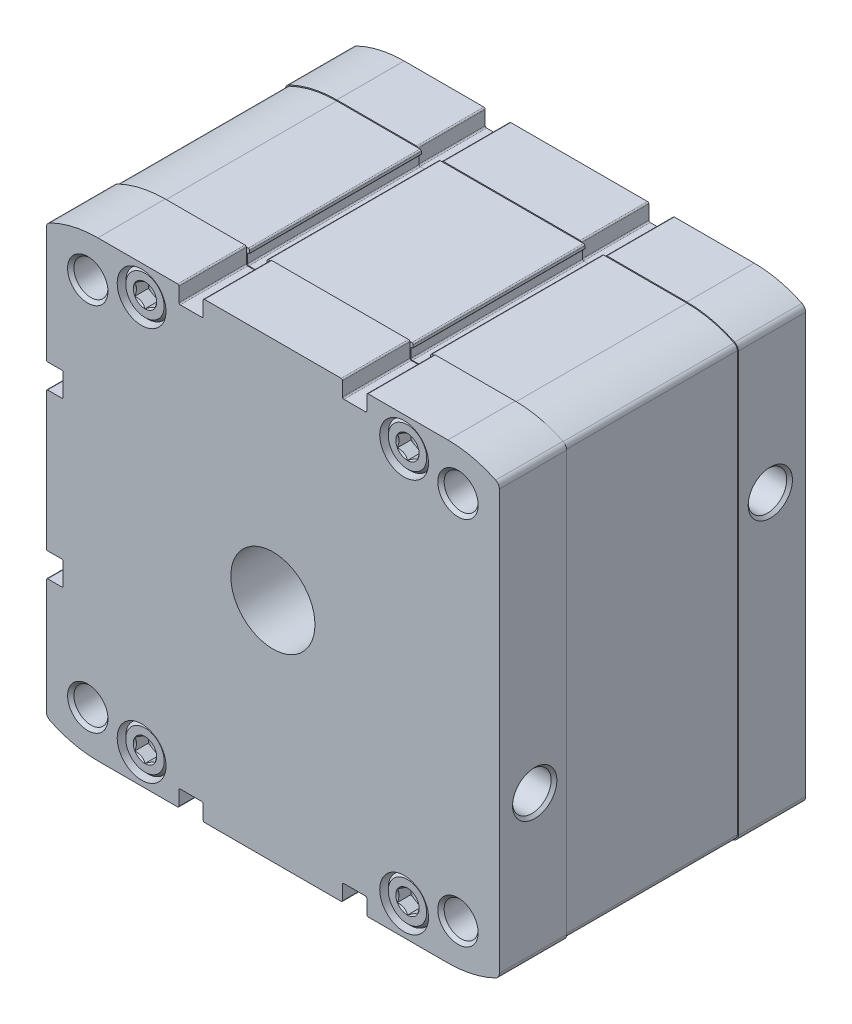
SolidWorks part; units mm, degrees
ref_plane "Front Plane" through (0, 0, 0) normal (0, 0, 1) x (1, 0, 0)
ref_plane "Top Plane" through (0, 0, 0) normal (0, 1, 0) x (1, 0, 0)
ref_plane "Right Plane" through (0, 0, 0) normal (1, 0, 0) x (0, 0, -1)
ref_plane "Plane1" through (0, 0, -20) normal (0, 0, 1) x (1, 0, 0)
ref_plane "Plane2" through (0, 0, -71) normal (0, 0, 1) x (1, 0, 0)
sketch "Sketch1" plane through (0, 0, 0) normal (0, 0, 1) x (1, 0, 0)
  line L0 (-66.9, 27.9) -> (-62.7, 27.9)
  line L1 (-62.3, 27.5) -> (-62.3, 21.1)
  line L2 (-62.7, 20.7) -> (-66.9, 20.7)
  line L3 (-67.3, 20.3) -> (-67.3, -20.3)
  line L4 (-66.9, -20.7) -> (-62.7, -20.7)
  line L5 (-62.3, -21.1) -> (-62.3, -27.5)
  line L6 (-62.7, -27.9) -> (-66.9, -27.9)
  line L7 (-67.3, -28.3) -> (-67.3, -62.3009)
  line L8 (-52, -67.3) -> (-28.3, -67.3)
  line L9 (-27.9, -66.9) -> (-27.9, -62.7)
  line L10 (-27.5, -62.3) -> (-21.1, -62.3)
  line L11 (-20.7, -62.7) -> (-20.7, -66.9)
  line L12 (-20.3, -67.3) -> (20.3, -67.3)
  line L13 (20.7, -66.9) -> (20.7, -62.7)
  line L14 (21.1, -62.3) -> (27.5, -62.3)
  line L15 (27.9, -62.7) -> (27.9, -66.9)
  line L16 (28.3, -67.3) -> (52, -67.3)
  line L17 (67.3, -62.3009) -> (67.3, 62.3009)
  line L18 (52, 67.3) -> (28.3, 67.3)
  line L19 (27.9, 66.9) -> (27.9, 62.7)
  line L20 (27.5, 62.3) -> (21.1, 62.3)
  line L21 (20.7, 62.7) -> (20.7, 66.9)
  line L22 (20.3, 67.3) -> (-20.3, 67.3)
  line L23 (-20.7, 66.9) -> (-20.7, 62.7)
  line L24 (-21.1, 62.3) -> (-27.5, 62.3)
  line L25 (-27.9, 62.7) -> (-27.9, 66.9)
  line L26 (-28.3, 67.3) -> (-52, 67.3)
  line L27 (-67.3, 62.3009) -> (-67.3, 28.3)
  arc A0 (-67.3, 28.3) -> (-66.9, 27.9) centre (-66.9, 28.3) ccw
  arc A1 (-62.7, 27.9) -> (-62.3, 27.5) centre (-62.7, 27.5) cw
  arc A2 (-62.3, 21.1) -> (-62.7, 20.7) centre (-62.7, 21.1) cw
  arc A3 (-66.9, 20.7) -> (-67.3, 20.3) centre (-66.9, 20.3) ccw
  arc A4 (-67.3, -20.3) -> (-66.9, -20.7) centre (-66.9, -20.3) ccw
  arc A5 (-62.7, -20.7) -> (-62.3, -21.1) centre (-62.7, -21.1) cw
  arc A6 (-62.3, -27.5) -> (-62.7, -27.9) centre (-62.7, -27.5) cw
  arc A7 (-66.9, -27.9) -> (-67.3, -28.3) centre (-66.9, -28.3) ccw
  arc A8 (-67.3, -62.3009) -> (-66.1966, -64.0575) centre (-65.35, -62.3009) ccw
  arc A9 (-66.1966, -64.0575) -> (-52, -67.3) centre (-52, -34.6) ccw
  arc A10 (-28.3, -67.3) -> (-27.9, -66.9) centre (-28.3, -66.9) ccw
  arc A11 (-27.9, -62.7) -> (-27.5, -62.3) centre (-27.5, -62.7) cw
  arc A12 (-21.1, -62.3) -> (-20.7, -62.7) centre (-21.1, -62.7) cw
  arc A13 (-20.7, -66.9) -> (-20.3, -67.3) centre (-20.3, -66.9) ccw
  arc A14 (20.3, -67.3) -> (20.7, -66.9) centre (20.3, -66.9) ccw
  arc A15 (20.7, -62.7) -> (21.1, -62.3) centre (21.1, -62.7) cw
  arc A16 (27.5, -62.3) -> (27.9, -62.7) centre (27.5, -62.7) cw
  arc A17 (27.9, -66.9) -> (28.3, -67.3) centre (28.3, -66.9) ccw
  arc A18 (52, -67.3) -> (66.1966, -64.0575) centre (52, -34.6) ccw
  arc A19 (66.1966, -64.0575) -> (67.3, -62.3009) centre (65.35, -62.3009) ccw
  arc A20 (67.3, 62.3009) -> (66.1966, 64.0575) centre (65.35, 62.3009) ccw
  arc A21 (66.1966, 64.0575) -> (52, 67.3) centre (52, 34.6) ccw
  arc A22 (28.3, 67.3) -> (27.9, 66.9) centre (28.3, 66.9) ccw
  arc A23 (27.9, 62.7) -> (27.5, 62.3) centre (27.5, 62.7) cw
  arc A24 (21.1, 62.3) -> (20.7, 62.7) centre (21.1, 62.7) cw
  arc A25 (20.7, 66.9) -> (20.3, 67.3) centre (20.3, 66.9) ccw
  arc A26 (-20.3, 67.3) -> (-20.7, 66.9) centre (-20.3, 66.9) ccw
  arc A27 (-20.7, 62.7) -> (-21.1, 62.3) centre (-21.1, 62.7) cw
  arc A28 (-27.5, 62.3) -> (-27.9, 62.7) centre (-27.5, 62.7) cw
  arc A29 (-27.9, 66.9) -> (-28.3, 67.3) centre (-28.3, 66.9) ccw
  arc A30 (-52, 67.3) -> (-66.1966, 64.0575) centre (-52, 34.6) ccw
  arc A31 (-66.1966, 64.0575) -> (-67.3, 62.3009) centre (-65.35, 62.3009) ccw
extrude "Boss-Extrude1" add sketch "Sketch1" against normal blind 91
sketch "Sketch2" plane through (0, 0, -20) normal (0, 0, 1) x (1, 0, 0)
  line L0 (-67, 67) -> (-67, -67)
  line L1 (-67, -67) -> (67, -67)
  line L2 (67, -67) -> (67, 67)
  line L3 (67, 67) -> (-67, 67)
extrude "Boss-Extrude2" add sketch "Sketch2" against normal blind 51
sketch "Sketch3" plane through (0, 0, -20) normal (0, 0, 1) x (1, 0, 0)
  line L0 (-100, 100) -> (-100, -100)
  line L1 (-100, -100) -> (100, -100)
  line L2 (100, -100) -> (100, 100)
  line L3 (100, 100) -> (-100, 100)
  line L4 (-66.6, 26.9) -> (-65.9, 26.9)
  line L5 (-65.7, 27.1) -> (-65.7, 27.35)
  line L6 (-65.5, 27.55) -> (-62.9, 27.55)
  line L7 (-62.5, 27.15) -> (-62.5, 21.45)
  line L8 (-62.9, 21.05) -> (-65.5, 21.05)
  line L9 (-65.7, 21.25) -> (-65.7, 21.5)
  line L10 (-65.9, 21.7) -> (-66.6, 21.7)
  line L11 (-67, 21.3) -> (-67, -21.3)
  line L12 (-66.6, -21.7) -> (-65.9, -21.7)
  line L13 (-65.7, -21.5) -> (-65.7, -21.25)
  line L14 (-65.5, -21.05) -> (-62.9, -21.05)
  line L15 (-62.5, -21.45) -> (-62.5, -27.15)
  line L16 (-62.9, -27.55) -> (-65.5, -27.55)
  line L17 (-65.7, -27.35) -> (-65.7, -27.1)
  line L18 (-65.9, -26.9) -> (-66.6, -26.9)
  line L19 (-67, -27.3) -> (-67, -62.2695)
  line L20 (-52, -67) -> (-27.3, -67)
  line L21 (-26.9, -66.6) -> (-26.9, -65.9)
  line L22 (-27.1, -65.7) -> (-27.35, -65.7)
  line L23 (-27.55, -65.5) -> (-27.55, -62.9)
  line L24 (-27.15, -62.5) -> (-21.45, -62.5)
  line L25 (-21.05, -62.9) -> (-21.05, -65.5)
  line L26 (-21.25, -65.7) -> (-21.5, -65.7)
  line L27 (-21.7, -65.9) -> (-21.7, -66.6)
  line L28 (-21.3, -67) -> (21.3, -67)
  line L29 (21.7, -66.6) -> (21.7, -65.9)
  line L30 (21.5, -65.7) -> (21.25, -65.7)
  line L31 (21.05, -65.5) -> (21.05, -62.9)
  line L32 (21.45, -62.5) -> (27.15, -62.5)
  line L33 (27.55, -62.9) -> (27.55, -65.5)
  line L34 (27.35, -65.7) -> (27.1, -65.7)
  line L35 (26.9, -65.9) -> (26.9, -66.6)
  line L36 (27.3, -67) -> (52, -67)
  line L37 (67, -62.2695) -> (67, 62.2695)
  line L38 (52, 67) -> (27.3, 67)
  line L39 (26.9, 66.6) -> (26.9, 65.9)
  line L40 (27.1, 65.7) -> (27.35, 65.7)
  line L41 (27.55, 65.5) -> (27.55, 62.9)
  line L42 (27.15, 62.5) -> (21.45, 62.5)
  line L43 (21.05, 62.9) -> (21.05, 65.5)
  line L44 (21.25, 65.7) -> (21.5, 65.7)
  line L45 (21.7, 65.9) -> (21.7, 66.6)
  line L46 (21.3, 67) -> (-21.3, 67)
  line L47 (-21.7, 66.6) -> (-21.7, 65.9)
  line L48 (-21.5, 65.7) -> (-21.25, 65.7)
  line L49 (-21.05, 65.5) -> (-21.05, 62.9)
  line L50 (-21.45, 62.5) -> (-27.15, 62.5)
  line L51 (-27.55, 62.9) -> (-27.55, 65.5)
  line L52 (-27.35, 65.7) -> (-27.1, 65.7)
  line L53 (-26.9, 65.9) -> (-26.9, 66.6)
  line L54 (-27.3, 67) -> (-52, 67)
  line L55 (-67, 62.2695) -> (-67, 27.3)
  arc A0 (-67, 27.3) -> (-66.6, 26.9) centre (-66.6, 27.3) ccw
  arc A1 (-65.9, 26.9) -> (-65.7, 27.1) centre (-65.9, 27.1) ccw
  arc A2 (-65.7, 27.35) -> (-65.5, 27.55) centre (-65.5, 27.35) cw
  arc A3 (-62.9, 27.55) -> (-62.5, 27.15) centre (-62.9, 27.15) cw
  arc A4 (-62.5, 21.45) -> (-62.9, 21.05) centre (-62.9, 21.45) cw
  arc A5 (-65.5, 21.05) -> (-65.7, 21.25) centre (-65.5, 21.25) cw
  arc A6 (-65.7, 21.5) -> (-65.9, 21.7) centre (-65.9, 21.5) ccw
  arc A7 (-66.6, 21.7) -> (-67, 21.3) centre (-66.6, 21.3) ccw
  arc A8 (-67, -21.3) -> (-66.6, -21.7) centre (-66.6, -21.3) ccw
  arc A9 (-65.9, -21.7) -> (-65.7, -21.5) centre (-65.9, -21.5) ccw
  arc A10 (-65.7, -21.25) -> (-65.5, -21.05) centre (-65.5, -21.25) cw
  arc A11 (-62.9, -21.05) -> (-62.5, -21.45) centre (-62.9, -21.45) cw
  arc A12 (-62.5, -27.15) -> (-62.9, -27.55) centre (-62.9, -27.15) cw
  arc A13 (-65.5, -27.55) -> (-65.7, -27.35) centre (-65.5, -27.35) cw
  arc A14 (-65.7, -27.1) -> (-65.9, -26.9) centre (-65.9, -27.1) ccw
  arc A15 (-66.6, -26.9) -> (-67, -27.3) centre (-66.6, -27.3) ccw
  arc A16 (-67, -62.2695) -> (-66.0365, -63.8017) centre (-65.3, -62.2695) ccw
  arc A17 (-66.0365, -63.8017) -> (-52, -67) centre (-52, -34.6) ccw
  arc A18 (-27.3, -67) -> (-26.9, -66.6) centre (-27.3, -66.6) ccw
  arc A19 (-26.9, -65.9) -> (-27.1, -65.7) centre (-27.1, -65.9) ccw
  arc A20 (-27.35, -65.7) -> (-27.55, -65.5) centre (-27.35, -65.5) cw
  arc A21 (-27.55, -62.9) -> (-27.15, -62.5) centre (-27.15, -62.9) cw
  arc A22 (-21.45, -62.5) -> (-21.05, -62.9) centre (-21.45, -62.9) cw
  arc A23 (-21.05, -65.5) -> (-21.25, -65.7) centre (-21.25, -65.5) cw
  arc A24 (-21.5, -65.7) -> (-21.7, -65.9) centre (-21.5, -65.9) ccw
  arc A25 (-21.7, -66.6) -> (-21.3, -67) centre (-21.3, -66.6) ccw
  arc A26 (21.3, -67) -> (21.7, -66.6) centre (21.3, -66.6) ccw
  arc A27 (21.7, -65.9) -> (21.5, -65.7) centre (21.5, -65.9) ccw
  arc A28 (21.25, -65.7) -> (21.05, -65.5) centre (21.25, -65.5) cw
  arc A29 (21.05, -62.9) -> (21.45, -62.5) centre (21.45, -62.9) cw
  arc A30 (27.15, -62.5) -> (27.55, -62.9) centre (27.15, -62.9) cw
  arc A31 (27.55, -65.5) -> (27.35, -65.7) centre (27.35, -65.5) cw
  arc A32 (27.1, -65.7) -> (26.9, -65.9) centre (27.1, -65.9) ccw
  arc A33 (26.9, -66.6) -> (27.3, -67) centre (27.3, -66.6) ccw
  arc A34 (52, -67) -> (66.0365, -63.8017) centre (52, -34.6) ccw
  arc A35 (66.0365, -63.8017) -> (67, -62.2695) centre (65.3, -62.2695) ccw
  arc A36 (67, 62.2695) -> (66.0365, 63.8017) centre (65.3, 62.2695) ccw
  arc A37 (66.0365, 63.8017) -> (52, 67) centre (52, 34.6) ccw
  arc A38 (27.3, 67) -> (26.9, 66.6) centre (27.3, 66.6) ccw
  arc A39 (26.9, 65.9) -> (27.1, 65.7) centre (27.1, 65.9) ccw
  arc A40 (27.35, 65.7) -> (27.55, 65.5) centre (27.35, 65.5) cw
  arc A41 (27.55, 62.9) -> (27.15, 62.5) centre (27.15, 62.9) cw
  arc A42 (21.45, 62.5) -> (21.05, 62.9) centre (21.45, 62.9) cw
  arc A43 (21.05, 65.5) -> (21.25, 65.7) centre (21.25, 65.5) cw
  arc A44 (21.5, 65.7) -> (21.7, 65.9) centre (21.5, 65.9) ccw
  arc A45 (21.7, 66.6) -> (21.3, 67) centre (21.3, 66.6) ccw
  arc A46 (-21.3, 67) -> (-21.7, 66.6) centre (-21.3, 66.6) ccw
  arc A47 (-21.7, 65.9) -> (-21.5, 65.7) centre (-21.5, 65.9) ccw
  arc A48 (-21.25, 65.7) -> (-21.05, 65.5) centre (-21.25, 65.5) cw
  arc A49 (-21.05, 62.9) -> (-21.45, 62.5) centre (-21.45, 62.9) cw
  arc A50 (-27.15, 62.5) -> (-27.55, 62.9) centre (-27.15, 62.9) cw
  arc A51 (-27.55, 65.5) -> (-27.35, 65.7) centre (-27.35, 65.5) cw
  arc A52 (-27.1, 65.7) -> (-26.9, 65.9) centre (-27.1, 65.9) ccw
  arc A53 (-26.9, 66.6) -> (-27.3, 67) centre (-27.3, 66.6) ccw
  arc A54 (-52, 67) -> (-66.0365, 63.8017) centre (-52, 34.6) ccw
  arc A55 (-66.0365, 63.8017) -> (-67, 62.2695) centre (-65.3, 62.2695) ccw
extrude "Cut-Extrude1" cut sketch "Sketch3" against normal blind 51
ref_plane "Plane3" through (0, -21.15, 0) normal (0, 1, 0) x (1, 0, 0)
ref_plane "Plane4" through (0, 21.15, 0) normal (0, 1, 0) x (1, 0, 0)
ref_plane "Plane5" through (67.3, 0, 0) normal (1, 0, 0) x (0, 0, -1)
ref_plane "Plane6" through (0, 0, -91) normal (0, 0, 1) x (1, 0, 0)
sketch "Sketch4" plane through (0, -21.15, 0) normal (0, 1, 0) x (1, 0, 0)
  line L0 (39.5, 10.5) -> (39.5, 16.2225)
  line L1 (39.5, 16.2225) -> (66.444, 16.2225)
  line L2 (66.444, 16.2225) -> (67.3, 17.0785)
  line L3 (67.3, 17.0785) -> (67.3, 10.5)
  line L4 (67.3, 10.5) -> (39.5, 10.5)
  line L5 (67.3, 10.5) -> (39.5, 10.5) construction
revolve "Cut-Revolve1" cut sketch "Sketch4" angle 360 about L5 reverse direction yes
cosmetic thread "Cosmetic Thread1" parameters "D1"=13, "D2"=13.157
sketch "Sketch5" plane through (0, 21.15, 0) normal (0, 1, 0) x (1, 0, 0)
  line L0 (39.5, 80.5) -> (39.5, 86.2225)
  line L1 (39.5, 86.2225) -> (66.444, 86.2225)
  line L2 (66.444, 86.2225) -> (67.3, 87.0785)
  line L3 (67.3, 87.0785) -> (67.3, 80.5)
  line L4 (67.3, 80.5) -> (39.5, 80.5)
  line L5 (67.3, 80.5) -> (39.5, 80.5) construction
revolve "Cut-Revolve2" cut sketch "Sketch5" angle 360 about L5 reverse direction yes
cosmetic thread "Cosmetic Thread2" parameters "D1"=13, "D2"=13.157
sketch "Sketch6" plane through (0, 0, 0) normal (1, 0, 0) x (0, 0, -1)
  line L0 (-1, 0) -> (-1, 12.5)
  line L1 (-1, 12.5) -> (28.75, 12.5)
  line L2 (28.75, 12.5) -> (28.75, 62.5)
  line L3 (28.75, 62.5) -> (70, 62.5)
  line L4 (70, 62.5) -> (70, 0)
  line L5 (70, 0) -> (-1, 0)
  line L6 (70, 0) -> (-1, 0) construction
revolve "Cut-Revolve3" cut sketch "Sketch6" angle 360 about L6 reverse direction yes
sketch "Sketch7" plane through (0, 0, 0) normal (1, 0, 0) x (0, 0, -1)
  line L0 (88.4, 0) -> (88.4, 6)
  line L1 (88.4, 6) -> (91, 6)
  line L2 (91, 6) -> (91, 0)
  line L3 (91, 0) -> (88.4, 0)
  line L4 (91, 0) -> (88.4, 0) construction
revolve "Cut-Revolve4" cut sketch "Sketch7" angle 360 about L4 reverse direction yes
ref_plane "Plane7" through (55, 0, 0) normal (1, 0, 0) x (0, 0, -1)
ref_plane "Plane8" through (-55, 0, 0) normal (1, 0, 0) x (0, 0, -1)
ref_plane "Plane9" through (0, 58.5, 0) normal (0, 1, 0) x (1, 0, 0)
ref_plane "Plane10" through (0, -58.5, 0) normal (0, 1, 0) x (1, 0, 0)
sketch "Sketch8" plane through (0, 58.5, 0) normal (0, 1, 0) x (1, 0, 0)
  line L0 (39, 5.8038) -> (42, 5)
  line L1 (42, 5) -> (42, 1.48)
  line L2 (42, 1.48) -> (42.48, 1)
  line L3 (42.48, 1) -> (44.7, 1)
  line L4 (44.7, 1) -> (45.5, 1.8)
  line L5 (45.5, 1.8) -> (45.5, 9)
  line L6 (45.5, 9) -> (46.25, 9)
  line L7 (46.25, 9) -> (46.25, -1)
  line L8 (46.25, -1) -> (39, -1)
  line L9 (39, -1) -> (39, 5.8038)
  line L10 (39, -1) -> (39, 5.8038) construction
revolve "Cut-Revolve5" cut sketch "Sketch8" angle 360 about L10 reverse direction yes
sketch "Sketch9" plane through (0, 58.5, 0) normal (0, 1, 0) x (1, 0, 0)
  line L0 (-39, 5.8038) -> (-36, 5)
  line L1 (-36, 5) -> (-36, 1.48)
  line L2 (-36, 1.48) -> (-35.52, 1)
  line L3 (-35.52, 1) -> (-33.3, 1)
  line L4 (-33.3, 1) -> (-32.5, 1.8)
  line L5 (-32.5, 1.8) -> (-32.5, 9)
  line L6 (-32.5, 9) -> (-31.75, 9)
  line L7 (-31.75, 9) -> (-31.75, -1)
  line L8 (-31.75, -1) -> (-39, -1)
  line L9 (-39, -1) -> (-39, 5.8038)
  line L10 (-39, -1) -> (-39, 5.8038) construction
revolve "Cut-Revolve6" cut sketch "Sketch9" angle 360 about L10 reverse direction yes
sketch "Sketch10" plane through (0, -58.5, 0) normal (0, 1, 0) x (1, 0, 0)
  line L0 (39, 5.8038) -> (42, 5)
  line L1 (42, 5) -> (42, 1.48)
  line L2 (42, 1.48) -> (42.48, 1)
  line L3 (42.48, 1) -> (44.7, 1)
  line L4 (44.7, 1) -> (45.5, 1.8)
  line L5 (45.5, 1.8) -> (45.5, 9)
  line L6 (45.5, 9) -> (46.25, 9)
  line L7 (46.25, 9) -> (46.25, -1)
  line L8 (46.25, -1) -> (39, -1)
  line L9 (39, -1) -> (39, 5.8038)
  line L10 (39, -1) -> (39, 5.8038) construction
revolve "Cut-Revolve7" cut sketch "Sketch10" angle 360 about L10 reverse direction yes
sketch "Sketch11" plane through (0, -58.5, 0) normal (0, 1, 0) x (1, 0, 0)
  line L0 (-39, 5.8038) -> (-36, 5)
  line L1 (-36, 5) -> (-36, 1.48)
  line L2 (-36, 1.48) -> (-35.52, 1)
  line L3 (-35.52, 1) -> (-33.3, 1)
  line L4 (-33.3, 1) -> (-32.5, 1.8)
  line L5 (-32.5, 1.8) -> (-32.5, 9)
  line L6 (-32.5, 9) -> (-31.75, 9)
  line L7 (-31.75, 9) -> (-31.75, -1)
  line L8 (-31.75, -1) -> (-39, -1)
  line L9 (-39, -1) -> (-39, 5.8038)
  line L10 (-39, -1) -> (-39, 5.8038) construction
revolve "Cut-Revolve8" cut sketch "Sketch11" angle 360 about L10 reverse direction yes
sketch "Sketch12" plane through (0, 58.5, 0) normal (0, 1, 0) x (1, 0, 0)
  line L0 (39, 92) -> (46.25, 92)
  line L1 (46.25, 92) -> (46.25, 82)
  line L2 (46.25, 82) -> (45.5, 82)
  line L3 (45.5, 82) -> (45.5, 89.2)
  line L4 (45.5, 89.2) -> (44.7, 90)
  line L5 (44.7, 90) -> (42.48, 90)
  line L6 (42.48, 90) -> (42, 89.52)
  line L7 (42, 89.52) -> (42, 86)
  line L8 (42, 86) -> (39, 85.1962)
  line L9 (39, 85.1962) -> (39, 92)
  line L10 (39, 85.1962) -> (39, 92) construction
revolve "Cut-Revolve9" cut sketch "Sketch12" angle 360 about L10 reverse direction yes
sketch "Sketch13" plane through (0, 58.5, 0) normal (0, 1, 0) x (1, 0, 0)
  line L0 (-39, 92) -> (-31.75, 92)
  line L1 (-31.75, 92) -> (-31.75, 82)
  line L2 (-31.75, 82) -> (-32.5, 82)
  line L3 (-32.5, 82) -> (-32.5, 89.2)
  line L4 (-32.5, 89.2) -> (-33.3, 90)
  line L5 (-33.3, 90) -> (-35.52, 90)
  line L6 (-35.52, 90) -> (-36, 89.52)
  line L7 (-36, 89.52) -> (-36, 86)
  line L8 (-36, 86) -> (-39, 85.1962)
  line L9 (-39, 85.1962) -> (-39, 92)
  line L10 (-39, 85.1962) -> (-39, 92) construction
revolve "Cut-Revolve10" cut sketch "Sketch13" angle 360 about L10 reverse direction yes
sketch "Sketch14" plane through (0, -58.5, 0) normal (0, 1, 0) x (1, 0, 0)
  line L0 (-39, 92) -> (-31.75, 92)
  line L1 (-31.75, 92) -> (-31.75, 82)
  line L2 (-31.75, 82) -> (-32.5, 82)
  line L3 (-32.5, 82) -> (-32.5, 89.2)
  line L4 (-32.5, 89.2) -> (-33.3, 90)
  line L5 (-33.3, 90) -> (-35.52, 90)
  line L6 (-35.52, 90) -> (-36, 89.52)
  line L7 (-36, 89.52) -> (-36, 86)
  line L8 (-36, 86) -> (-39, 85.1962)
  line L9 (-39, 85.1962) -> (-39, 92)
  line L10 (-39, 85.1962) -> (-39, 92) construction
revolve "Cut-Revolve11" cut sketch "Sketch14" angle 360 about L10 reverse direction yes
sketch "Sketch15" plane through (0, -58.5, 0) normal (0, 1, 0) x (1, 0, 0)
  line L0 (39, 92) -> (46.25, 92)
  line L1 (46.25, 92) -> (46.25, 82)
  line L2 (46.25, 82) -> (45.5, 82)
  line L3 (45.5, 82) -> (45.5, 89.2)
  line L4 (45.5, 89.2) -> (44.7, 90)
  line L5 (44.7, 90) -> (42.48, 90)
  line L6 (42.48, 90) -> (42, 89.52)
  line L7 (42, 89.52) -> (42, 86)
  line L8 (42, 86) -> (39, 85.1962)
  line L9 (39, 85.1962) -> (39, 92)
  line L10 (39, 85.1962) -> (39, 92) construction
revolve "Cut-Revolve12" cut sketch "Sketch15" angle 360 about L10 reverse direction yes
ref_plane "Plane11" through (0, 0, -1) normal (0, 0, 1) x (1, 0, 0)
sketch "Sketch16" plane through (0, 0, -1) normal (0, 0, 1) x (1, 0, 0)
  line L0 (36, 56.7679) -> (39, 55.0359)
  line L1 (39, 55.0359) -> (42, 56.7679)
  line L2 (42, 56.7679) -> (42, 60.2321)
  line L3 (42, 60.2321) -> (39, 61.9641)
  line L4 (39, 61.9641) -> (36, 60.2321)
  line L5 (36, 60.2321) -> (36, 56.7679)
extrude "Cut-Extrude2" cut sketch "Sketch16" against normal blind 4
sketch "Sketch17" plane through (0, 0, -1) normal (0, 0, 1) x (1, 0, 0)
  line L0 (-42, 56.7679) -> (-39, 55.0359)
  line L1 (-39, 55.0359) -> (-36, 56.7679)
  line L2 (-36, 56.7679) -> (-36, 60.2321)
  line L3 (-36, 60.2321) -> (-39, 61.9641)
  line L4 (-39, 61.9641) -> (-42, 60.2321)
  line L5 (-42, 60.2321) -> (-42, 56.7679)
extrude "Cut-Extrude3" cut sketch "Sketch17" against normal blind 4
sketch "Sketch18" plane through (0, 0, -1) normal (0, 0, 1) x (1, 0, 0)
  line L0 (-42, -60.2321) -> (-39, -61.9641)
  line L1 (-39, -61.9641) -> (-36, -60.2321)
  line L2 (-36, -60.2321) -> (-36, -56.7679)
  line L3 (-36, -56.7679) -> (-39, -55.0359)
  line L4 (-39, -55.0359) -> (-42, -56.7679)
  line L5 (-42, -56.7679) -> (-42, -60.2321)
extrude "Cut-Extrude4" cut sketch "Sketch18" against normal blind 4
sketch "Sketch19" plane through (0, 0, -1) normal (0, 0, 1) x (1, 0, 0)
  line L0 (36, -60.2321) -> (39, -61.9641)
  line L1 (39, -61.9641) -> (42, -60.2321)
  line L2 (42, -60.2321) -> (42, -56.7679)
  line L3 (42, -56.7679) -> (39, -55.0359)
  line L4 (39, -55.0359) -> (36, -56.7679)
  line L5 (36, -56.7679) -> (36, -60.2321)
extrude "Cut-Extrude5" cut sketch "Sketch19" against normal blind 4
ref_plane "Plane12" through (0, 0, -90) normal (0, 0, 1) x (1, 0, 0)
sketch "Sketch20" plane through (0, 0, -90) normal (0, 0, 1) x (1, 0, 0)
  line L0 (36, 56.7679) -> (39, 55.0359)
  line L1 (39, 55.0359) -> (42, 56.7679)
  line L2 (42, 56.7679) -> (42, 60.2321)
  line L3 (42, 60.2321) -> (39, 61.9641)
  line L4 (39, 61.9641) -> (36, 60.2321)
  line L5 (36, 60.2321) -> (36, 56.7679)
extrude "Cut-Extrude6" cut sketch "Sketch20" along normal blind 4
sketch "Sketch21" plane through (0, 0, -90) normal (0, 0, 1) x (1, 0, 0)
  line L0 (-42, 56.7679) -> (-39, 55.0359)
  line L1 (-39, 55.0359) -> (-36, 56.7679)
  line L2 (-36, 56.7679) -> (-36, 60.2321)
  line L3 (-36, 60.2321) -> (-39, 61.9641)
  line L4 (-39, 61.9641) -> (-42, 60.2321)
  line L5 (-42, 60.2321) -> (-42, 56.7679)
extrude "Cut-Extrude7" cut sketch "Sketch21" along normal blind 4
sketch "Sketch22" plane through (0, 0, -90) normal (0, 0, 1) x (1, 0, 0)
  line L0 (-42, -60.2321) -> (-39, -61.9641)
  line L1 (-39, -61.9641) -> (-36, -60.2321)
  line L2 (-36, -60.2321) -> (-36, -56.7679)
  line L3 (-36, -56.7679) -> (-39, -55.0359)
  line L4 (-39, -55.0359) -> (-42, -56.7679)
  line L5 (-42, -56.7679) -> (-42, -60.2321)
extrude "Cut-Extrude8" cut sketch "Sketch22" along normal blind 4
sketch "Sketch23" plane through (0, 0, -90) normal (0, 0, 1) x (1, 0, 0)
  line L0 (36, -60.2321) -> (39, -61.9641)
  line L1 (39, -61.9641) -> (42, -60.2321)
  line L2 (42, -60.2321) -> (42, -56.7679)
  line L3 (42, -56.7679) -> (39, -55.0359)
  line L4 (39, -55.0359) -> (36, -56.7679)
  line L5 (36, -56.7679) -> (36, -60.2321)
extrude "Cut-Extrude9" cut sketch "Sketch23" along normal blind 4
ref_plane "Plane13" through (0, 0, -91) normal (0, 0, 1) x (1, 0, 0)
sketch "Sketch24" plane through (55, 0, 0) normal (1, 0, 0) x (0, 0, -1)
  line L0 (0, 55) -> (0, 61)
  line L1 (0, 61) -> (0.947, 60.053)
  line L2 (0.947, 60.053) -> (20, 60.053)
  line L3 (20, 60.053) -> (20, 55)
  line L4 (20, 55) -> (0, 55)
  line L5 (20, 55) -> (0, 55) construction
revolve "Cut-Revolve13" cut sketch "Sketch24" angle 360 about L5 reverse direction yes
cosmetic thread "Cosmetic Thread3" parameters "D1"=20, "D2"=12
sketch "Sketch25" plane through (-55, 0, 0) normal (1, 0, 0) x (0, 0, -1)
  line L0 (0, 55) -> (0, 61)
  line L1 (0, 61) -> (0.947, 60.053)
  line L2 (0.947, 60.053) -> (20, 60.053)
  line L3 (20, 60.053) -> (20, 55)
  line L4 (20, 55) -> (0, 55)
  line L5 (20, 55) -> (0, 55) construction
revolve "Cut-Revolve14" cut sketch "Sketch25" angle 360 about L5 reverse direction yes
cosmetic thread "Cosmetic Thread4" parameters "D1"=20, "D2"=12
sketch "Sketch26" plane through (55, 0, 0) normal (1, 0, 0) x (0, 0, -1)
  line L0 (0, -55) -> (0, -49)
  line L1 (0, -49) -> (0.947, -49.947)
  line L2 (0.947, -49.947) -> (20, -49.947)
  line L3 (20, -49.947) -> (20, -55)
  line L4 (20, -55) -> (0, -55)
  line L5 (20, -55) -> (0, -55) construction
revolve "Cut-Revolve15" cut sketch "Sketch26" angle 360 about L5 reverse direction yes
cosmetic thread "Cosmetic Thread5" parameters "D1"=20, "D2"=12
sketch "Sketch27" plane through (-55, 0, 0) normal (1, 0, 0) x (0, 0, -1)
  line L0 (0, -55) -> (0, -49)
  line L1 (0, -49) -> (0.947, -49.947)
  line L2 (0.947, -49.947) -> (20, -49.947)
  line L3 (20, -49.947) -> (20, -55)
  line L4 (20, -55) -> (0, -55)
  line L5 (20, -55) -> (0, -55) construction
revolve "Cut-Revolve16" cut sketch "Sketch27" angle 360 about L5 reverse direction yes
cosmetic thread "Cosmetic Thread6" parameters "D1"=20, "D2"=12
sketch "Sketch28" plane through (55, 0, 0) normal (1, 0, 0) x (0, 0, -1)
  line L0 (71, 55) -> (71, 60.053)
  line L1 (71, 60.053) -> (90.053, 60.053)
  line L2 (90.053, 60.053) -> (91, 61)
  line L3 (91, 61) -> (91, 55)
  line L4 (91, 55) -> (71, 55)
  line L5 (91, 55) -> (71, 55) construction
revolve "Cut-Revolve17" cut sketch "Sketch28" angle 360 about L5 reverse direction yes
cosmetic thread "Cosmetic Thread7" parameters "D1"=20, "D2"=12
sketch "Sketch29" plane through (55, 0, 0) normal (1, 0, 0) x (0, 0, -1)
  line L0 (20, 55) -> (20, 60.5)
  line L1 (20, 60.5) -> (71, 60.5)
  line L2 (71, 60.5) -> (71, 55)
  line L3 (71, 55) -> (20, 55)
  line L4 (71, 55) -> (20, 55) construction
revolve "Cut-Revolve18" cut sketch "Sketch29" angle 360 about L4 reverse direction yes
sketch "Sketch30" plane through (-55, 0, 0) normal (1, 0, 0) x (0, 0, -1)
  line L0 (71, 55) -> (71, 60.053)
  line L1 (71, 60.053) -> (90.053, 60.053)
  line L2 (90.053, 60.053) -> (91, 61)
  line L3 (91, 61) -> (91, 55)
  line L4 (91, 55) -> (71, 55)
  line L5 (91, 55) -> (71, 55) construction
revolve "Cut-Revolve19" cut sketch "Sketch30" angle 360 about L5 reverse direction yes
cosmetic thread "Cosmetic Thread8" parameters "D1"=20, "D2"=12
sketch "Sketch31" plane through (-55, 0, 0) normal (1, 0, 0) x (0, 0, -1)
  line L0 (20, 55) -> (20, 60.5)
  line L1 (20, 60.5) -> (71, 60.5)
  line L2 (71, 60.5) -> (71, 55)
  line L3 (71, 55) -> (20, 55)
  line L4 (71, 55) -> (20, 55) construction
revolve "Cut-Revolve20" cut sketch "Sketch31" angle 360 about L4 reverse direction yes
sketch "Sketch32" plane through (55, 0, 0) normal (1, 0, 0) x (0, 0, -1)
  line L0 (71, -55) -> (71, -49.947)
  line L1 (71, -49.947) -> (90.053, -49.947)
  line L2 (90.053, -49.947) -> (91, -49)
  line L3 (91, -49) -> (91, -55)
  line L4 (91, -55) -> (71, -55)
  line L5 (91, -55) -> (71, -55) construction
revolve "Cut-Revolve21" cut sketch "Sketch32" angle 360 about L5 reverse direction yes
cosmetic thread "Cosmetic Thread9" parameters "D1"=20, "D2"=12
sketch "Sketch33" plane through (55, 0, 0) normal (1, 0, 0) x (0, 0, -1)
  line L0 (20, -55) -> (20, -49.5)
  line L1 (20, -49.5) -> (71, -49.5)
  line L2 (71, -49.5) -> (71, -55)
  line L3 (71, -55) -> (20, -55)
  line L4 (71, -55) -> (20, -55) construction
revolve "Cut-Revolve22" cut sketch "Sketch33" angle 360 about L4 reverse direction yes
sketch "Sketch34" plane through (-55, 0, 0) normal (1, 0, 0) x (0, 0, -1)
  line L0 (71, -55) -> (71, -49.947)
  line L1 (71, -49.947) -> (90.053, -49.947)
  line L2 (90.053, -49.947) -> (91, -49)
  line L3 (91, -49) -> (91, -55)
  line L4 (91, -55) -> (71, -55)
  line L5 (91, -55) -> (71, -55) construction
revolve "Cut-Revolve23" cut sketch "Sketch34" angle 360 about L5 reverse direction yes
cosmetic thread "Cosmetic Thread10" parameters "D1"=20, "D2"=12
sketch "Sketch35" plane through (-55, 0, 0) normal (1, 0, 0) x (0, 0, -1)
  line L0 (20, -55) -> (20, -49.5)
  line L1 (20, -49.5) -> (71, -49.5)
  line L2 (71, -49.5) -> (71, -55)
  line L3 (71, -55) -> (20, -55)
  line L4 (71, -55) -> (20, -55) construction
revolve "Cut-Revolve24" cut sketch "Sketch35" angle 360 about L4 reverse direction yes
ref_plane "Plane14" through (0, 0, -70) normal (0, 0, 1) x (1, 0, 0)
ref_plane "Plane15" through (67.3, 0, 0) normal (1, 0, 0) x (0, 0, -1)
ref_plane "Plane16" through (0, 0, -91) normal (0, 0, 1) x (1, 0, 0)
ref_plane "Plane17" through (0, 0, 0) normal (0, 0, 1) x (1, 0, 0)
ref_plane "Plane18" through (0, 0, 0) normal (0, 0, 1) x (1, 0, 0)
ref_plane "Plane19" through (0, 0, 0) normal (1, 0, 0) x (0, 0, -1)
ref_plane "Plane20" through (67.3, 0, 0) normal (1, 0, 0) x (0, 0, -1)
ref_plane "CYLINDER XY" through (0, 0, -70) normal (0, 0, 1) x (1, 0, 0)
ref_plane "CYLINDER XZ" through (0, 0, 0) normal (0, -1, 0) x (-1, 0, 0)
ref_plane "CYLINDER YZ" through (0, 0, 0) normal (1, 0, 0) x (0, 0, -1)
ref_axis "CYLINDER X" through (-80.9, 0, -70) along (1, 0, 0)
ref_axis "CYLINDER Y" through (0, -50, -70) along (0, 1, 0)
ref_axis "CYLINDER Z" through (0, 0, 80.9) along (0, 0, -1)
sketch3d "CYLINDER"
  point P0 (0, 0, -70)
ref_plane "FDT_FRONT XY" through (0, 0, 0) normal (0, 0, 1) x (1, 0, 0)
ref_plane "FDT_FRONT XZ" through (0, 0, 0) normal (-1, 0, 0) x (0, 0, 1)
ref_plane "FDT_FRONT YZ" through (0, 0, 0) normal (0, -1, 0) x (-1, 0, 0)
ref_axis "FDT_FRONT X" through (0, 50, 0) along (0, -1, 0)
ref_axis "FDT_FRONT Y" through (-80.9, 0, 0) along (1, 0, 0)
ref_axis "FDT_FRONT Z" through (0, 0, 50) along (0, 0, -1)
sketch3d "FDT_FRONT"
  point P0 (0, 0, 0)
ref_plane "FDT_QSFRONT XY" through (67.3, 0, 0) normal (1, 0, 0) x (0, 0, -1)
ref_plane "FDT_QSFRONT XZ" through (0, 0, -10.5) normal (0, 0, 1) x (1, 0, 0)
ref_plane "FDT_QSFRONT YZ" through (0, -21.15, 0) normal (0, -1, 0) x (-1, 0, 0)
ref_axis "FDT_QSFRONT X" through (67.3, 50, -10.5) along (0, -1, 0)
ref_axis "FDT_QSFRONT Y" through (67.3, -21.15, 80.9) along (0, 0, -1)
ref_axis "FDT_QSFRONT Z" through (80.9, -21.15, -10.5) along (-1, 0, 0)
sketch3d "FDT_QSFRONT"
  point P0 (67.3, -21.15, -10.5)
ref_plane "FDT_QSREAR XY" through (67.3, 0, 0) normal (1, 0, 0) x (0, 0, -1)
ref_plane "FDT_QSREAR XZ" through (0, 0, -80.5) normal (0, 0, 1) x (1, 0, 0)
ref_plane "FDT_QSREAR YZ" through (0, 21.15, 0) normal (0, -1, 0) x (-1, 0, 0)
ref_axis "FDT_QSREAR X" through (67.3, 50, -80.5) along (0, -1, 0)
ref_axis "FDT_QSREAR Y" through (67.3, 21.15, 80.9) along (0, 0, -1)
ref_axis "FDT_QSREAR Z" through (80.9, 21.15, -80.5) along (-1, 0, 0)
sketch3d "FDT_QSREAR"
  point P0 (67.3, 21.15, -80.5)
ref_plane "FDT_REAR XY" through (0, 0, -91) normal (0, 0, 1) x (1, 0, 0)
ref_plane "FDT_REAR XZ" through (0, 0, 0) normal (-1, 0, 0) x (0, 0, 1)
ref_plane "FDT_REAR YZ" through (0, 0, 0) normal (0, -1, 0) x (-1, 0, 0)
ref_axis "FDT_REAR X" through (0, 50, -91) along (0, -1, 0)
ref_axis "FDT_REAR Y" through (-80.9, 0, -91) along (1, 0, 0)
ref_axis "FDT_REAR Z" through (0, 0, 50) along (0, 0, -1)
sketch3d "FDT_REAR"
  point P0 (0, 0, -91)
ref_plane "FDT_SLOT3 XY" through (0, 62.3, 0) normal (0, 1, 0) x (1, 0, 0)
ref_plane "FDT_SLOT3 XZ" through (0, 0, -45.5) normal (0, 0, 1) x (1, 0, 0)
ref_plane "FDT_SLOT3 YZ" through (24.3, 0, 0) normal (1, 0, 0) x (0, 0, -1)
ref_axis "FDT_SLOT3 X" through (-80.9, 62.3, -45.5) along (1, 0, 0)
ref_axis "FDT_SLOT3 Y" through (24.3, 62.3, 50) along (0, 0, -1)
ref_axis "FDT_SLOT3 Z" through (24.3, 50, -45.5) along (0, -1, 0)
sketch3d "FDT_SLOT3"
  point P0 (24.3, 62.3, -45.5)
ref_plane "FDT_SLOT4 XY" through (0, 62.3, 0) normal (0, 1, 0) x (1, 0, 0)
ref_plane "FDT_SLOT4 XZ" through (0, 0, -45.5) normal (0, 0, 1) x (1, 0, 0)
ref_plane "FDT_SLOT4 YZ" through (-24.3, 0, 0) normal (1, 0, 0) x (0, 0, -1)
ref_axis "FDT_SLOT4 X" through (-80.9, 62.3, -45.5) along (1, 0, 0)
ref_axis "FDT_SLOT4 Y" through (-24.3, 62.3, 50) along (0, 0, -1)
ref_axis "FDT_SLOT4 Z" through (-24.3, 50, -45.5) along (0, -1, 0)
sketch3d "FDT_SLOT4"
  point P0 (-24.3, 62.3, -45.5)
ref_plane "FDT_SLOT5 XY" through (-62.3, 0, 0) normal (-1, 0, 0) x (0, 0, 1)
ref_plane "FDT_SLOT5 XZ" through (0, 0, -45.5) normal (0, 0, 1) x (1, 0, 0)
ref_plane "FDT_SLOT5 YZ" through (0, 24.3, 0) normal (0, 1, 0) x (1, 0, 0)
ref_axis "FDT_SLOT5 X" through (-62.3, -50, -45.5) along (0, 1, 0)
ref_axis "FDT_SLOT5 Y" through (-62.3, 24.3, 80.9) along (0, 0, -1)
ref_axis "FDT_SLOT5 Z" through (-80.9, 24.3, -45.5) along (1, 0, 0)
sketch3d "FDT_SLOT5"
  point P0 (-62.3, 24.3, -45.5)
ref_plane "FDT_SLOT6 XY" through (-62.3, 0, 0) normal (-1, 0, 0) x (0, 0, 1)
ref_plane "FDT_SLOT6 XZ" through (0, 0, -45.5) normal (0, 0, 1) x (1, 0, 0)
ref_plane "FDT_SLOT6 YZ" through (0, -24.3, 0) normal (0, 1, 0) x (1, 0, 0)
ref_axis "FDT_SLOT6 X" through (-62.3, -50, -45.5) along (0, 1, 0)
ref_axis "FDT_SLOT6 Y" through (-62.3, -24.3, 80.9) along (0, 0, -1)
ref_axis "FDT_SLOT6 Z" through (-80.9, -24.3, -45.5) along (1, 0, 0)
sketch3d "FDT_SLOT6"
  point P0 (-62.3, -24.3, -45.5)
ref_plane "FDT_SLOT7 XY" through (0, -62.3, 0) normal (0, -1, 0) x (-1, 0, 0)
ref_plane "FDT_SLOT7 XZ" through (0, 0, -45.5) normal (0, 0, 1) x (1, 0, 0)
ref_plane "FDT_SLOT7 YZ" through (-24.3, 0, 0) normal (-1, 0, 0) x (0, 0, 1)
ref_axis "FDT_SLOT7 X" through (80.9, -62.3, -45.5) along (-1, 0, 0)
ref_axis "FDT_SLOT7 Y" through (-24.3, -62.3, 50) along (0, 0, -1)
ref_axis "FDT_SLOT7 Z" through (-24.3, -50, -45.5) along (0, 1, 0)
sketch3d "FDT_SLOT7"
  point P0 (-24.3, -62.3, -45.5)
ref_plane "FDT_SLOT8 XY" through (0, -62.3, 0) normal (0, -1, 0) x (-1, 0, 0)
ref_plane "FDT_SLOT8 XZ" through (0, 0, -45.5) normal (0, 0, 1) x (1, 0, 0)
ref_plane "FDT_SLOT8 YZ" through (24.3, 0, 0) normal (-1, 0, 0) x (0, 0, 1)
ref_axis "FDT_SLOT8 X" through (80.9, -62.3, -45.5) along (-1, 0, 0)
ref_axis "FDT_SLOT8 Y" through (24.3, -62.3, 50) along (0, 0, -1)
ref_axis "FDT_SLOT8 Z" through (24.3, -50, -45.5) along (0, 1, 0)
sketch3d "FDT_SLOT8"
  point P0 (24.3, -62.3, -45.5)
ref_plane "TO_DUMMY XY" through (0, 0, 0) normal (0, 0, 1) x (1, 0, 0)
ref_plane "TO_DUMMY XZ" through (0, 0, 0) normal (0, -1, 0) x (-1, 0, 0)
ref_plane "TO_DUMMY YZ" through (0, 0, 0) normal (1, 0, 0) x (0, 0, -1)
ref_axis "TO_DUMMY X" through (-80.9, 0, 0) along (1, 0, 0)
ref_axis "TO_DUMMY Y" through (0, -50, 0) along (0, 1, 0)
ref_axis "TO_DUMMY Z" through (0, 0, 80.9) along (0, 0, -1)
sketch3d "TO_DUMMY"
  point P0 (0, 0, 0)
other "Freeze***"
